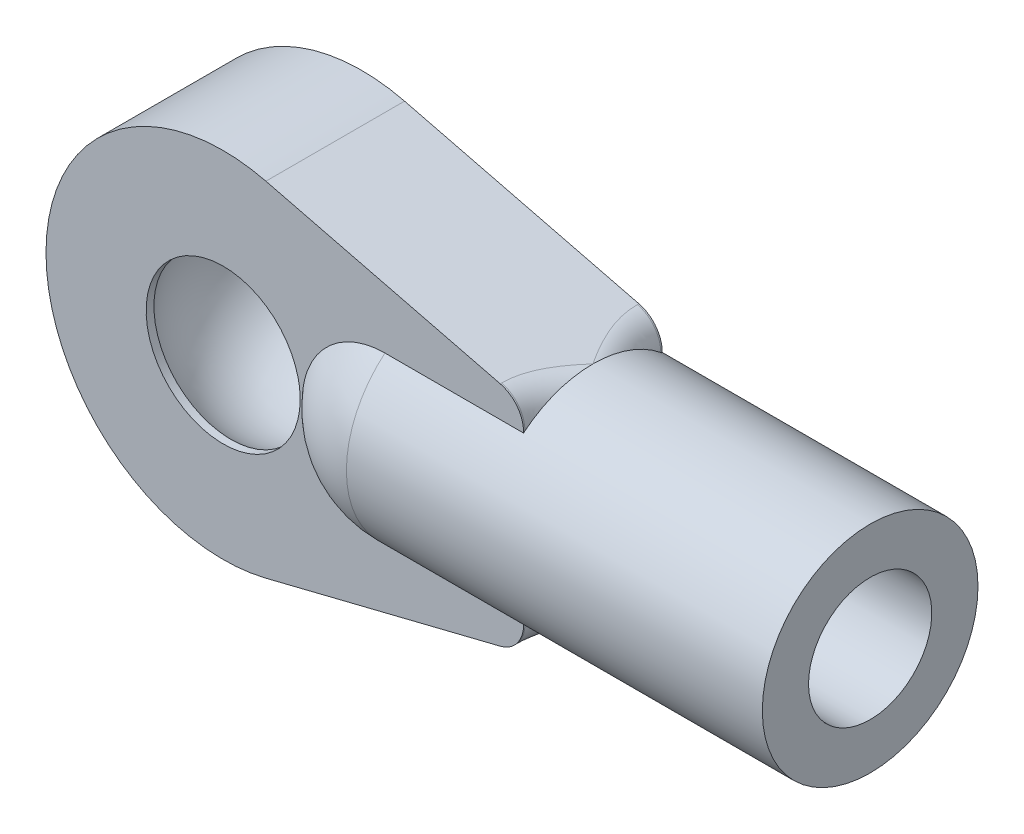
SolidWorks part; units mm, degrees
ref_plane "Front" through (0, 0, 0) normal (0, 0, 1) x (1, 0, 0)
ref_plane "Top" through (0, 0, 0) normal (0, 1, 0) x (1, 0, 0)
ref_plane "Right" through (0, 0, 0) normal (1, 0, 0) x (0, 0, -1)
sketch "Sketch1" plane through (0, 0, 0) normal (0, 0, 1) x (1, 0, 0)
  line L0 (0, 0) -> (14482.9519, 0) construction
  line L1 (0, 0) -> (0, 2)
  line L2 (0, 2) -> (13.5, 2)
  line L3 (13.5, 2) -> (13.5, 3.5)
  line L4 (13.5, 3.5) -> (0, 3.5)
  line L5 (-3.5, 0) -> (0, 0)
  arc A0 (0, 3.5) -> (-3.5, 0) centre (0, 0) ccw
  dimension "D1" = 4
  dimension "D2" = 7
  dimension "D3" = 13.5
revolve "Revolve1" add sketch "Sketch1" angle 360 about L0
sketch "Sketch2" plane through (0, 0, 0) normal (0, 0, 1) x (1, 0, 0)
  line L0 (13.5, -3.5) -> (13.5, 3.5) construction
  line L1 (-3.862, 5.58) -> (4.5, 3.5)
  line L3 (4.5, -3.5) -> (-3.862, -5.58)
  line L4 (4.5, 3.5) -> (4.5, -3.5)
  line L5 (0, -3.5) -> (13.5, -3.5) construction
  line L6 (13.5, -2) -> (13.5, 2) construction
  circle A0 centre (-5.25, 0) radius 2.5
  circle A1 centre (-5.25, 0) radius 5.75 construction
  arc A3 (-3.862, 5.58) -> (-3.862, -5.58) centre (-5.25, 0) ccw
  point P0 (4.5, 0)
  point P3 (-11, 0)
  dimension "D2" = 5.75
  dimension "D3" = 5
  dimension "D1" = 24.5
  dimension "D4" = 9
extrude "Boss-Extrude1" add sketch "Sketch2" along normal mid plane 4.5 separate body
combine bodies "Combine1" operation type add bodies to combine 101 102
fillet "Fillet1" radius 1 4 edges at (4.5, -3.5, -1.125) (4.5, -3.5, 1.125) (4.5, 3.5, -1.125) (4.5, 3.5, 1.125)
ref_axis "Axis1" through (-5.25, 0, 2.25) along (0, 0, -1)
ref_plane "Plane1" through (-5.25, 0, 0) normal (1, 0, 0) x (0, 0, -1)
sketch "Sketch3" plane through (-5.25, 0, 0) normal (1, 0, 0) x (0, 0, -1)
  line L0 (0, 0) -> (50000, 0) construction
  line L1 (3.2, 0) -> (-3.2, 0)
  arc A0 (2.25, -2.681) -> (2.25, 2.681) centre (0, 0) ccw construction
  arc A1 (3.2, 0) -> (-3.2, 0) centre (0, 0) ccw
  point P6 (3.5, 0)
  dimension "D1" = 3.2
revolve "Cut-Revolve1" cut sketch "Sketch3" angle 360 about L0
